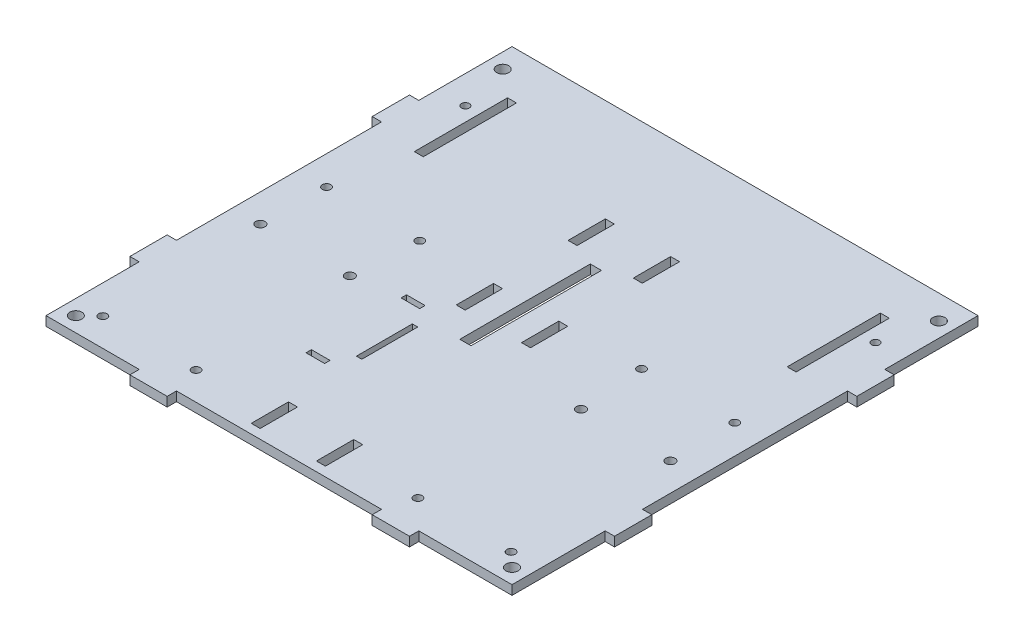
SolidWorks part; units mm, degrees
ref_plane "Front Plane" through (0, 0, 0) normal (0, 0, 1) x (1, 0, 0)
ref_plane "Top Plane" through (0, 0, 0) normal (0, 1, 0) x (1, 0, 0)
ref_plane "Right Plane" through (0, 0, 0) normal (1, 0, 0) x (0, 0, -1)
sketch "Sketch1" plane through (0, 0, 0) normal (0, 1, 0) x (1, 0, 0)
  line L0 (144.9, 25) -> (144.9, 5)
  line L1 (144.9, 5) -> (140.1, 5)
  line L2 (140.1, 25) -> (144.9, 25)
  line L3 (140.1, 5) -> (140.1, 25)
  line L4 (109.9, 5) -> (109.9, 25)
  line L5 (109.9, 25) -> (105.1, 25)
  line L6 (105.1, 25) -> (105.1, 5)
  line L7 (105.1, 5) -> (109.9, 5)
  line L8 (87, 52.4842) -> (97, 52.4842)
  line L9 (97, 55.3842) -> (97, 52.4842)
  line L10 (87, 55.3842) -> (97, 55.3842)
  line L11 (87, 52.4842) -> (87, 55.3842)
  line L12 (105, 64.4342) -> (102.1, 64.4342)
  line L13 (105, 64.4342) -> (105, 94.4342)
  line L14 (102.1, 94.4342) -> (102.1, 64.4342)
  line L15 (102.1, 94.4342) -> (105, 94.4342)
  line L16 (97, 106.3842) -> (97, 103.4842)
  line L17 (97, 106.3842) -> (87, 106.3842)
  line L18 (87, 103.4842) -> (97, 103.4842)
  line L19 (87, 103.4842) -> (87, 106.3842)
  line L20 (109.9, 135) -> (105.1, 135)
  line L21 (109.9, 115) -> (109.9, 135)
  line L22 (105.1, 135) -> (105.1, 115)
  line L23 (105.1, 115) -> (109.9, 115)
  line L24 (144.9, 115) -> (140.1, 115)
  line L25 (140.1, 115) -> (140.1, 135)
  line L26 (144.9, 135) -> (144.9, 115)
  line L27 (140.1, 135) -> (144.9, 135)
  line L28 (227.4, 175) -> (227.4, 225)
  line L29 (222.6, 175) -> (222.6, 225)
  line L30 (227.4, 225) -> (222.6, 225)
  line L31 (222.6, 175) -> (227.4, 175)
  line L32 (125, 100) -> (125, 170) construction
  line L33 (122, 170) -> (128, 170)
  line L34 (122, 170) -> (122, 100)
  line L35 (122, 100) -> (128, 100)
  line L36 (22.6, 225) -> (27.4, 225)
  line L37 (27.4, 225) -> (27.4, 175)
  line L38 (22.6, 175) -> (22.6, 225)
  line L39 (27.4, 175) -> (22.6, 175)
  line L40 (250, 250) -> (0, 250)
  line L41 (0, 250) -> (0, 0)
  line L42 (0, 0) -> (250, 0)
  line L43 (250, 0) -> (250, 250)
  line L44 (128, 170) -> (128, 100)
  dimension "D2" = 22.6
  dimension "D3" = 5.1
  dimension "D4" = 10
  dimension "D5" = 102.1
  dimension "D6" = 2.9
  dimension "D7" = 27.4
  dimension "D8" = 105.1
  dimension "D9" = 4.8
  dimension "D10" = 140.1
  dimension "D11" = 222.6
  dimension "D12" = 5
  dimension "D13" = 25
  dimension "D14" = 52.4842
  dimension "D15" = 250
  dimension "D16" = 64.4342
  dimension "D17" = 103.4842
  dimension "D18" = 94.4342
  dimension "D19" = 115
  dimension "D20" = 50
  dimension "D21" = 6
  dimension "D22" = 70
  dimension "D23" = 175
  dimension "D24" = 125
  dimension "D25" = 250
  dimension "D26" = 80
extrude "Boss-Extrude1" add sketch "Sketch1" along normal blind 5
sketch "Sketch2" plane through (0, 5, 0) normal (0, 1, 0) x (1, 0, 0)
  line L0 (0, 250) -> (0, 0) construction
  line L1 (0, 0) -> (250, 0) construction
  circle A0 centre (15, 100) radius 2.5
  circle A1 centre (63, 100) radius 2.5
  dimension "D1" = 5
  dimension "D2" = 5
  dimension "D3" = 48
  dimension "D4" = 15
  dimension "D5" = 100
extrude "Cut-Extrude1" cut sketch "Sketch2" against normal through all
sketch "Sketch3" plane through (0, 5, 0) normal (0, 1, 0) x (1, 0, 0)
  line L3 (250, 0) -> (250, 250) construction
  circle A0 centre (8, 8) radius 3.25
  circle A1 centre (8, 237) radius 3.25
  dimension "D1" = 6.5
  dimension "D2" = 242
  dimension "D3" = 212
  dimension "D4" = 17
extrude "Cut-Extrude2" cut sketch "Sketch3" against normal through all
ref_plane "Plane1" through (125, 0, 0) normal (-1, 0, 0) x (0, 0, 1)
mirror "Mirror1" about plane through (125, 0, 0) normal (-1, 0, 0) of "Cut-Extrude2"
sketch "Sketch4" plane through (0, 5, 0) normal (0, 1, 0) x (1, 0, 0)
  line L1 (0, 200) -> (-5, 200)
  line L2 (0, 200) -> (0, 180)
  line L3 (0, 180) -> (-5, 180)
  line L4 (-5, 200) -> (-5, 180)
  line L7 (0, 70) -> (-5, 70)
  line L8 (0, 70) -> (0, 50)
  line L9 (0, 50) -> (-5, 50)
  line L10 (-5, 70) -> (-5, 50)
  line L11 (144.9, 5) -> (144.9, 25) construction
  line L12 (50, 0) -> (70, 0)
  line L13 (50, 0) -> (50, -5)
  line L14 (50, -5) -> (70, -5)
  line L15 (70, 0) -> (70, -5)
  line L16 (144.9, 25) -> (140.1, 25) construction
  dimension "D1" = 74.9
  dimension "D2" = 94.9
  dimension "D3" = 144.9
  dimension "D4" = 149.9
  dimension "D5" = 25
  dimension "D6" = 155
  dimension "D7" = 25
extrude "Boss-Extrude2" add sketch "Sketch4" against normal up to vertex (5 mm away) up to point (0, 0, 0)
mirror "Mirror2" about plane through (125, 0, 0) normal (-1, 0, 0) of "Boss-Extrude2"
mirror "Mirror3" about plane through (125, 0, 0) normal (-1, 0, 0) of "Cut-Extrude1"
hole_wizard "Ø4.5 (4.5) Diameter Hole1" positions "Sketch7" profile "Sketch6" hole size "Ø4.5" standard "ISO"
sketch "Sketch7" plane through (0, 5, 0) normal (0, 1, 0) x (1, 0, 0)
  line L0 (255, 200) -> (255, 180) construction
  line L1 (250, 200) -> (255, 200) construction
  point P0 (15.5, 135)
  point P3 (65.5, 135)
  point P6 (65.5, 15)
  point P9 (15.5, 15)
  dimension "D1" = 189.5
  dimension "D2" = 239.5
  dimension "D3" = 65
  dimension "D4" = 185
sketch "Sketch6" plane through (15.5, 5, -135) normal (1, 0, 0) x (0, 0, 1)
  line L0 (0, 0) -> (0, 11.3519)
  line L1 (0, 11.3519) -> (2.25, 10)
  line L2 (2.25, 10) -> (2.25, 0)
  line L5 (2.25, 0) -> (0, 0)
  line L10 (0, 11.3519) -> (-2.25, 10) construction
  line L11 (0, -6.35) -> (0, 107.95) construction
  dimension "Hole Dia." = 4.5
  dimension "Hole Depth" = 10
  dimension "Drill Angle" = 118
mirror "Mirror4" about plane through (125, 0, 0) normal (-1, 0, 0) of "Ø4.5 (4.5) Diameter Hole1"
sketch "Sketch9" plane through (0, 0, 0) normal (0, -1, 0) x (1, 0, 0)
  line L0 (105, -175) -> (110, -175) construction
  line L1 (105.1, -175) -> (109.9, -175)
  line L2 (105.1, -175) -> (105.1, -195)
  line L3 (105.1, -195) -> (109.9, -195)
  line L4 (109.9, -175) -> (109.9, -195)
  line L5 (105, -195) -> (110, -195) construction
  line L6 (105, -175) -> (105, -195) construction
  dimension "D1" = 4.8
  dimension "D2" = 0.1
extrude "Cut-Extrude3" cut sketch "Sketch9" against normal through all
mirror "Mirror5" about plane through (125, 0, 0) normal (-1, 0, 0) of "Cut-Extrude3"
sketch "Sketch10" plane through (0, 0, 0) normal (0, -1, 0) x (1, 0, 0)
  line L0 (0, -250) -> (0, 10) construction
  line L1 (250, -250) -> (0, -250) construction
  line L2 (250, -250) -> (250, 10) construction
  circle A0 centre (15, -210) radius 2.1
  circle A1 centre (235, -210) radius 2.1
  dimension "D1" = 4.2
  dimension "D2" = 15
  dimension "D3" = 40
  dimension "D4" = 15
extrude "Cut-Extrude4" cut sketch "Sketch10" against normal blind 5
